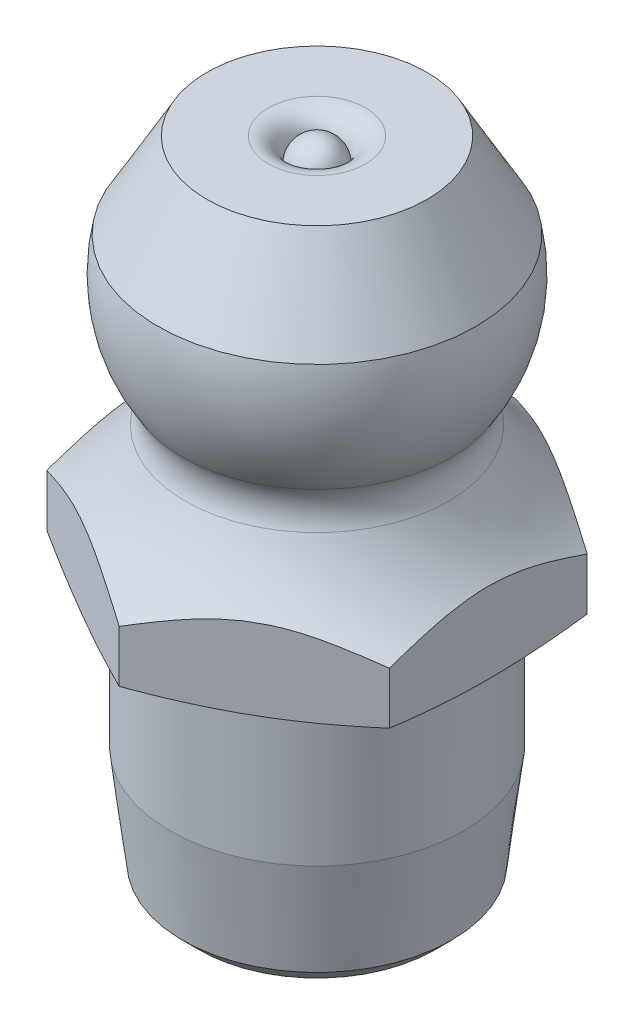
SolidWorks part; units mm, degrees
ref_plane "Plane1" through (0, 0, 0) normal (0, 0, 1) x (1, 0, 0)
ref_plane "Plane2" through (0, 0, 0) normal (0, 1, 0) x (1, 0, 0)
ref_plane "Plane3" through (0, 0, 0) normal (1, 0, 0) x (0, 0, -1)
sketch "support-top" plane through (0, 0, 0) normal (0, 1, 0) x (1, 0, 0)
  line L0 (0, -4.0415) -> (0, 4.0415) construction
  line L1 (0, 4.0415) -> (3.5, 2.0207)
  line L2 (3.5, 2.0207) -> (3.5, -2.0207)
  line L3 (3.5, -2.0207) -> (0, -4.0415)
  line L4 (-3.5, -2.0207) -> (0, -4.0415)
  line L5 (-3.5, 2.0207) -> (-3.5, -2.0207)
  line L6 (0, 4.0415) -> (-3.5, 2.0207)
  line L7 (4.0415, 0) -> (-4, 0) construction
  circle A0 centre (0, 0) radius 4.0415 construction
  circle A1 centre (0, 0) radius 3
  dimension "diam-thread" = 6
  dimension "width-key" = 7
sketch "support-front" plane through (0, 0, 0) normal (0, 0, 1) x (1, 0, 0)
  line L0 (0, 0) -> (0, 14.0771) construction
  line L1 (0.9928, 13.2) -> (2.25, 13.2)
  line L2 (0, 13.2) -> (-2.25, 13.2) construction
  line L3 (2.25, 13.2) -> (3.25, 11.4526)
  line L4 (-2.25, 13.2) -> (-3.25, 11.4526) construction
  line L5 (0, 10.7526) -> (3.3245, 10.7526) construction
  line L6 (0, 0) -> (2.7053, 0)
  line L7 (2.7053, 0) -> (3, 2.4)
  line L8 (-2.5, 8.5611) -> (2.5, 8.5611) construction
  line L9 (3, 5.2) -> (-3, 5.2) construction
  line L10 (3, 5.2) -> (4.0415, 5.4791)
  line L11 (0, 6.0103) -> (4.0415, 6.0103) construction
  line L12 (4.0415, 5.4791) -> (4.0415, 6.5415)
  line L13 (3, 2.4) -> (3.3438, 5.2) construction
  line L14 (-2.7053, 0) -> (0, 0) construction
  line L15 (-3, 2.4) -> (3, 2.4) construction
  line L16 (-4.0415, 5.4791) -> (-4.0415, 6.5415) construction
  line L17 (-3, 5.2) -> (-4.0415, 5.4791) construction
  line L18 (0, 12.7036) -> (2.5341, 12.7036) construction
  line L19 (0, 0) -> (0, 13.2)
  line L20 (3, 2.4) -> (3, 5.2)
  line L21 (-3, 2.4) -> (-3, 5.2) construction
  line L22 (3, 2.4) -> (3, 0) construction
  line L23 (-2.7053, 0) -> (-3, 2.4) construction
  line L24 (3, 5.2) -> (3.3438, 5.2) construction
  line L25 (2.4095, 0) -> (2.7467, 0.3373)
  line L26 (0, 0) -> (2.7467, 0.3373) construction
  arc A0 (3.25, 11.4526) -> (2.5, 8.5611) centre (0, 10.7526) ccw construction
  arc A1 (2.697, 8.086) -> (4.0415, 6.5415) centre (6.2858, 9.8526) ccw
  arc A2 (-2.697, 8.086) -> (-4.0415, 6.5415) centre (-6.2858, 9.8526) cw construction
  arc A3 (2.7524, 8.888) -> (3.25, 11.4526) centre (0, 10.7526) ccw
  arc A4 (2.7524, 8.888) -> (2.697, 8.086) centre (3.4148, 8.4393) ccw
  arc A5 (-2.7524, 8.888) -> (-2.697, 8.086) centre (-3.4148, 8.4393) cw construction
  arc A6 (0, 13.2) -> (0.4964, 12.7036) centre (0, 12.7036) cw
  arc A7 (0.4964, 12.7036) -> (0.9928, 13.2) centre (0.9928, 12.7036) cw
  dimension "rad-body" = 4
  dimension "rad-ball-start" = 0.8
  dimension "diam-top-ball" = 4.5
  dimension "diam-ball" = 6.5
  dimension "dist-angle-ball" = 0.7
  dimension "height" = 13.2
  dimension "dist-rad-body" = 0.9
  dimension "diam-ball-start" = 5
  dimension "angle-thread" = 7
  dimension "dist-thread" = 2.4
  dimension "length-thread" = 5.2
  dimension "D14" = 0.4964
  dimension "D10" = 15
  dimension "D2" = 45
  dimension "D3" = 7
sketch "support-thread" plane through (0, 0, 0) normal (0, 0, 1) x (1, 0, 0)
  line L0 (3.3881, 4.6901) -> (2.4607, 4.6901) construction
  line L1 (3.4589, 5.2664) -> (2.4607, 4.6901)
  line L2 (3.3267, 4.1901) -> (2.4607, 4.6901)
  line L3 (2.6772, 4.8151) -> (2.6772, 4.5651)
  line L4 (3.4589, 5.2664) -> (3.3267, 4.1901)
  line L5 (3.3267, 4.1901) -> (4.2541, 4.1901) construction
  line L6 (3.3267, 4.1901) -> (2.4607, 3.6901)
  line L8 (3.2269, 4.2478) -> (3.2116, 4.1237)
  line L9 (3, 2.4) -> (3.3438, 5.2) construction
  arc A0 (2.6231, 4.7839) -> (2.6231, 4.5964) centre (2.6772, 4.6901) ccw
  point P7 (2.6772, 4.6901)
  dimension "angle-thread" = 60
  dimension "pitch" = 1
  dimension "width-thread-bottom" = 0.25
  dimension "width-thread-top" = 0.125
ref_plane "support-plane-thread" through (0, 5.2, 0) normal (0, 1, 0) x (-1, 0, 0)
sketch "Sketch6" plane through (0, 0, 0) normal (0, 0, 1) x (1, 0, 0)
  line L0 (0, 0) -> (0, 13.2) construction
  line L1 (0.9928, 13.2) -> (2.25, 13.2) construction
  line L2 (2.25, 13.2) -> (3.25, 11.4526) construction
  line L3 (4.0415, 5.4791) -> (4.0415, 6.5415) construction
  line L4 (3, 5.2) -> (4.0415, 5.4791) construction
  line L6 (0, 0) -> (2.7053, 0) construction
  line L7 (0, 0) -> (0, 13.2) construction
  line L8 (0.9928, 13.2) -> (2.25, 13.2)
  line L9 (2.25, 13.2) -> (3.25, 11.4526)
  line L10 (4.0415, 5.4791) -> (4.0415, 6.5415)
  line L11 (3, 5.2) -> (4.0415, 5.4791)
  line L12 (3, 2.4) -> (3, 5.2) construction
  line L13 (0, 0) -> (2.4095, 0)
  line L14 (0, 0) -> (0, 13.2)
  line L15 (2.7053, 0) -> (3, 2.4) construction
  line L16 (3, 2.4) -> (3, 5.2)
  line L17 (2.7467, 0.3373) -> (3, 2.4)
  line L18 (2.4095, 0) -> (2.7467, 0.3373) construction
  line L19 (2.4095, 0) -> (2.7467, 0.3373)
  arc A0 (0.4964, 12.7036) -> (0, 13.2) centre (0, 12.7036) ccw construction
  arc A1 (0.9928, 13.2) -> (0.4964, 12.7036) centre (0.9928, 12.7036) ccw construction
  arc A2 (2.7524, 8.888) -> (3.25, 11.4526) centre (0, 10.7526) ccw construction
  arc A3 (2.7524, 8.888) -> (2.697, 8.086) centre (3.4148, 8.4393) ccw construction
  arc A4 (2.697, 8.086) -> (4.0415, 6.5415) centre (6.2858, 9.8526) ccw construction
  arc A5 (0.4964, 12.7036) -> (0, 13.2) centre (0, 12.7036) ccw
  arc A6 (0.9928, 13.2) -> (0.4964, 12.7036) centre (0.9928, 12.7036) ccw
  arc A7 (2.7524, 8.888) -> (3.25, 11.4526) centre (0, 10.7526) ccw
  arc A8 (2.7524, 8.888) -> (2.697, 8.086) centre (3.4148, 8.4393) ccw
  arc A9 (2.697, 8.086) -> (4.0415, 6.5415) centre (6.2858, 9.8526) ccw
revolve "body" add sketch "Sketch6" angle 360 about L7
sketch "Sketch4" plane through (0, 0, 0) normal (0, 1, 0) x (1, 0, 0)
  line L6 (3.5, -2.0207) -> (3.5, 2.0207)
  line L7 (3.5, 2.0207) -> (0, 4.0415)
  line L8 (0, 4.0415) -> (-3.5, 2.0207)
  line L9 (-3.5, 2.0207) -> (-3.5, -2.0207)
  line L10 (-3.5, -2.0207) -> (0, -4.0415)
  line L11 (0, -4.0415) -> (3.5, -2.0207)
  line L12 (3.5, -2.0207) -> (3.5, 2.0207)
  line L13 (3.5, 2.0207) -> (0, 4.0415)
  line L14 (0, 4.0415) -> (-3.5, 2.0207)
  line L15 (-3.5, 2.0207) -> (-3.5, -2.0207)
  line L16 (-3.5, -2.0207) -> (0, -4.0415)
  line L17 (0, -4.0415) -> (3.5, -2.0207)
  dimension "D1" = 0
extrude "cut-key" cut sketch "Sketch4" along normal through all flip side to cut
sketch "Sketch11" plane through (0, 0, 0) normal (0, 0, 1) x (1, 0, 0)
  line L0 (3, 5.2) -> (4.0415, 5.4791) construction
  line L1 (3, 2.4) -> (3, 5.2) construction
  line L2 (3, 5.2) -> (3.1917, 5.2514)
  line L3 (3, 5.0015) -> (3, 5.2)
  line L4 (3.4589, 5.2664) -> (2.4607, 4.6901) construction
  line L5 (0, 0) -> (0, 13.2) construction
  line L6 (0, 0) -> (0, 13.2) construction
  arc A0 (3, 5.0015) -> (3.1917, 5.2514) centre (3.2587, 5.0015) cw
revolve "body-fillet" [suppressed] add sketch "Sketch11" angle 360 about L6
sketch "Sketch8" plane through (0, 0, 0) normal (0, 0, 1) x (1, 0, 0)
  line L0 (0, 0) -> (0, 13.2) construction
  line L3 (3.3267, 4.1901) -> (2.4607, 4.6901) construction
  line L4 (3.4589, 5.2664) -> (2.4607, 4.6901) construction
  line L5 (0, 0) -> (0, 13.2) construction
  line L6 (3.2269, 4.2478) -> (3.2116, 4.1237) construction
  line L7 (3.2269, 4.2478) -> (3.3438, 5.2)
  line L8 (3.2269, 4.2478) -> (2.6231, 4.5964)
  line L9 (3.3438, 5.2) -> (2.6231, 4.7839)
  arc A0 (2.6231, 4.7839) -> (2.6231, 4.5964) centre (2.6772, 4.6901) ccw construction
  arc A1 (2.6231, 4.7839) -> (2.6231, 4.5964) centre (2.6772, 4.6901) ccw
revolve "thread-notch" [suppressed] cut sketch "Sketch8" angle 360 about L5
sketch "Sketch9" plane through (0, 5.2, 0) normal (0, 1, 0) x (-1, 0, 0)
  circle A0 centre (0, 0) radius 3 construction
  circle A1 centre (0, 0) radius 3
curve "helix" parameters "height-thread"=5.7, "pitch"=1
sketch "Sketch10" plane through (0, 0, 0) normal (0, 0, 1) x (1, 0, 0)
  line L2 (3.4589, 5.2664) -> (2.4607, 4.6901) construction
  line L3 (3.3267, 4.1901) -> (2.4607, 4.6901) construction
  line L6 (3.3438, 5.2) -> (2.6231, 4.7839)
  line L7 (3.2269, 4.2478) -> (2.6231, 4.5964)
  line L11 (3, 2.4) -> (3.3438, 5.2) construction
  line L12 (3.2269, 4.2478) -> (3.3438, 5.2)
  arc A0 (2.6231, 4.7839) -> (2.6231, 4.5964) centre (2.6772, 4.6901) ccw construction
  arc A1 (2.6231, 4.7839) -> (2.6231, 4.5964) centre (2.6772, 4.6901) ccw
sweep "thread-helix" [suppressed] cut profiles "Sketch10" path "helix"
ref_plane "ref-plane-top" through (0, 5.2, 0) normal (0, 1, 0) x (-1, 0, 0)
ref_axis "ref-axis-center" through (0, -50, 0) along (0, 1, 0)
ref_axis "ref-axis-lubrication" through (0, -50, 0) along (0, 1, 0)
equation "\"width-thread-bottom@support-thread\" = \"pitch@support-thread\" / 4"
equation "\"width-thread-top@support-thread\" = \"pitch@support-thread\" / 8"
equation "\"pitch@helix\" = \"pitch@support-thread\""
equation "\"height-thread@helix\" = \"length-thread@support-front\" + 0.5"
